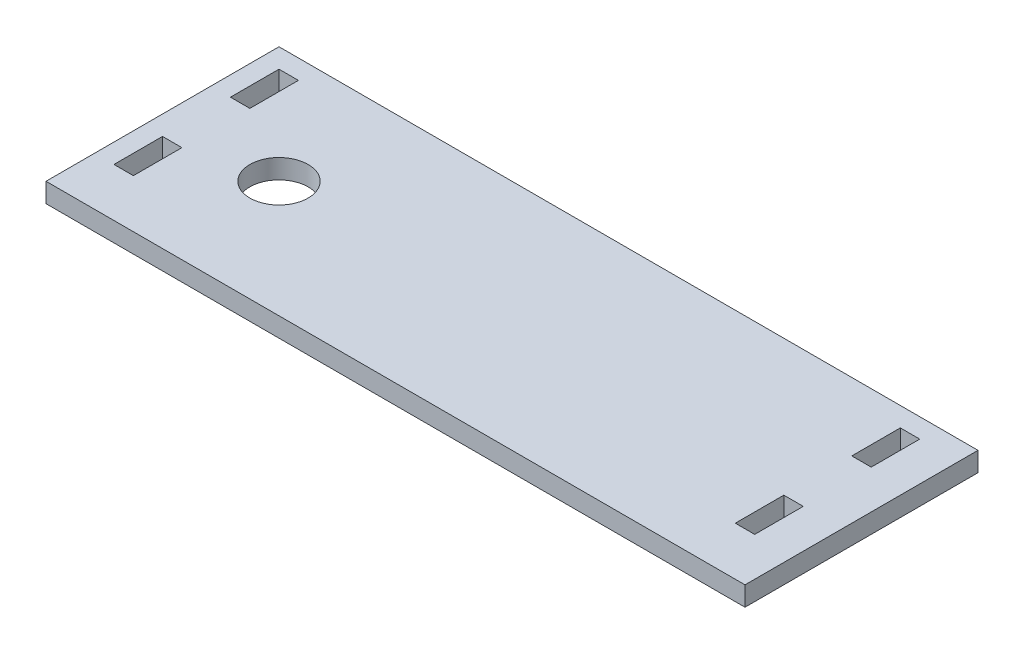
SolidWorks part; units mm, degrees
ref_plane "Front Plane" through (0, 0, 0) normal (0, 0, 1) x (1, 0, 0)
ref_plane "Top Plane" through (0, 0, 0) normal (0, 1, 0) x (1, 0, 0)
ref_plane "Right Plane" through (0, 0, 0) normal (1, 0, 0) x (0, 0, -1)
sketch "Sketch1" plane through (0, 0, 0) normal (0, 1, 0) x (1, 0, 0)
  line L0 (-107.95, -6.35) -> (-101.6, -6.35)
  line L1 (-114.3, 38.1) -> (114.3, 38.1)
  line L2 (-114.3, 38.1) -> (-114.3, -38.1)
  line L3 (-114.3, -38.1) -> (114.3, -38.1)
  line L4 (114.3, 38.1) -> (114.3, -38.1)
  line L5 (-107.95, 31.75) -> (-101.6, 31.75)
  line L6 (-107.95, 31.75) -> (-107.95, 15.875)
  line L7 (-107.95, 15.875) -> (-101.6, 15.875)
  line L8 (-101.6, 31.75) -> (-101.6, 15.875)
  line L9 (-107.95, -6.35) -> (-107.95, -22.225)
  line L10 (-107.95, -22.225) -> (-101.6, -22.225)
  line L11 (-101.6, -6.35) -> (-101.6, -22.225)
  line L13 (95.25, 31.75) -> (101.6, 31.75)
  line L14 (95.25, 31.75) -> (95.25, 15.875)
  line L15 (95.25, 15.875) -> (101.6, 15.875)
  line L16 (101.6, 31.75) -> (101.6, 15.875)
  line L17 (95.25, -6.35) -> (101.6, -6.35)
  line L18 (95.25, -6.35) -> (95.25, -22.225)
  line L19 (95.25, -22.225) -> (101.6, -22.225)
  line L20 (101.6, -6.35) -> (101.6, -22.225)
  circle A0 centre (-76.2, 0) radius 9.525
  point P7 (-114.3, 0)
  point P13 (0, 38.1)
  dimension "D1" = 19.05
  dimension "D2" = 6.35
  dimension "D3" = 38.1
  dimension "D4" = 190.5
  dimension "D5" = 6.35
  dimension "D6" = 15.875
  dimension "D7" = 6.35
  dimension "D8" = 38.1
  dimension "D9" = 22.225
  dimension "D10" = 196.85
extrude "Boss-Extrude1" add sketch "Sketch1" along normal blind 6.35
